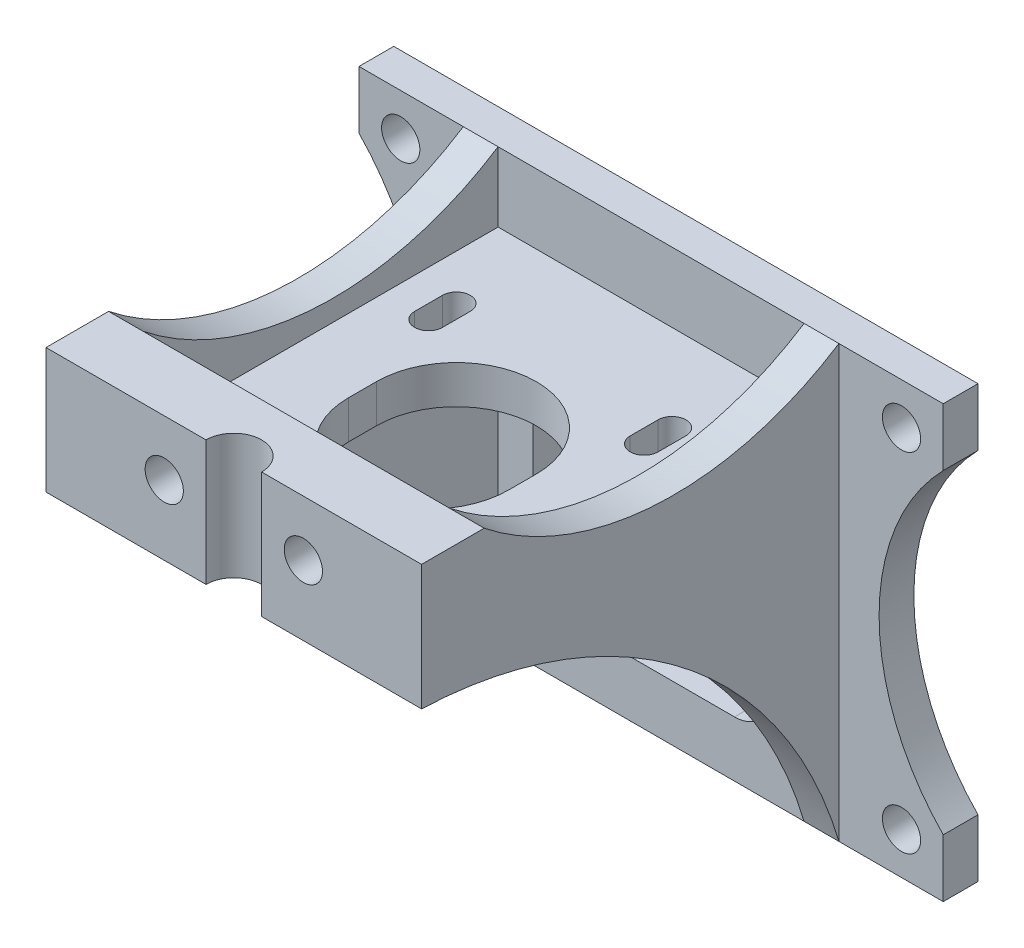
SolidWorks part; units mm, degrees
ref_plane "Front Plane" through (0, 0, 0) normal (0, 0, 1) x (1, 0, 0)
ref_plane "Top Plane" through (0, 0, 0) normal (0, 1, 0) x (1, 0, 0)
ref_plane "Right Plane" through (0, 0, 0) normal (1, 0, 0) x (0, 0, -1)
sketch "Sketch1" plane through (0, 0, 0) normal (1, 0, 0) x (0, 0, -1)
  line L0 (0, 0) -> (0, -62)
  line L1 (0, -62) -> (-5, -62)
  line L3 (-5, 0) -> (0, 0)
  line L4 (-56, 2.5) -> (-65, 2.5)
  line L5 (-65, 2.5) -> (-65, -15.5)
  arc A0 (-5, 0) -> (-56, 2.5) centre (-28.7567, 36.813) cw
  arc A1 (-5, -62) -> (-65, -15.5) centre (-67.324, -80.4584) ccw
  dimension "D3" = 51
  dimension "D5" = 43.813
  dimension "D8" = 65
  dimension "D1" = 5
  dimension "D2" = 62
  dimension "D4" = 2.5
  dimension "D6" = 9
  dimension "D7" = 18
  dimension "D9" = 5
extrude "Boss-Extrude1" add sketch "Sketch1" along normal blind 42 and the other way blind 42
sketch "Sketch2" plane through (0, 0, 0) normal (0, 0, -1) x (-1, 0, 0)
  line L0 (42, -62) -> (-42, -62) construction
  line L1 (-12, -54) -> (12, -54)
  line L2 (-17, -49) -> (-17, -25.5)
  line L3 (-12, -20.5) -> (12, -20.5)
  line L4 (17, -49) -> (17, -25.5)
  line L5 (42, -62) -> (42, 0) construction
  line L6 (42, 0) -> (-42, 0) construction
  line L7 (-42, -62) -> (-42, 0) construction
  line L8 (42, 2.5) -> (-42, 2.5) construction
  line L9 (-42, 0) -> (-27, 0)
  line L10 (-42, 0) -> (-42, 2.5)
  line L11 (-42, 2.5) -> (-27, 2.5)
  line L12 (-27, 0) -> (-27, 2.5)
  line L14 (42, 0) -> (27, 0)
  line L15 (42, 0) -> (42, 2.5)
  line L16 (42, 2.5) -> (27, 2.5)
  line L17 (27, 0) -> (27, 2.5)
  circle A0 centre (-36, -6) radius 2.75
  circle A1 centre (36, -6) radius 2.75
  circle A2 centre (36, -56) radius 2.75
  circle A3 centre (-36, -56) radius 2.75
  arc A4 (12, -20.5) -> (17, -25.5) centre (12, -25.5) cw
  arc A5 (12, -54) -> (17, -49) centre (12, -49) ccw
  arc A6 (-12, -54) -> (-17, -49) centre (-12, -49) cw
  arc A7 (-17, -25.5) -> (-12, -20.5) centre (-12, -25.5) cw
  arc A8 (-42, -8.3208) -> (-42, -53.6792) centre (-65.2788, -31) cw
  arc A9 (42, -8.3208) -> (42, -53.6792) centre (65.2788, -31) ccw
  line M7 (42, 0) -> (-42, 0)
  line M8 (-42, 0) -> (-42, -62)
  line M10 (42, -62) -> (42, 0)
  dimension "D1" = 5.5
  dimension "D2" = 5.5
  dimension "D3" = 5.5
  dimension "D4" = 5.5
  dimension "D9" = 5
  dimension "D18" = 8.3208
  dimension "D20" = 32.5
  dimension "D21" = 8.3208
  dimension "D23" = 32.5
  dimension "D5" = 33.5
  dimension "D6" = 34
  dimension "D7" = 8
  dimension "D8" = 25
  dimension "D10" = 6
  dimension "D11" = 6
  dimension "D12" = 6
  dimension "D13" = 6
  dimension "D14" = 6
  dimension "D15" = 6
  dimension "D16" = 6
  dimension "D17" = 6
  dimension "D19" = 8.3208
  dimension "D22" = 8.3208
  dimension "D24" = 15
  dimension "D25" = 15
extrude "Cut-Extrude1" cut sketch "Sketch2" against normal through all contours A0 | A8 M8 | A7 L2 A6 L1 A5 L4 A4 L3 | A3 | A2 | A1 | L17 L15 L16 M7 | L12 L11 L10 M7 | A9 M10 region at (0, -37.25, 0) region at (34.5, 1.25, 0) region at (-38.2626, -31, 0) region at (-34.5, 1.25, 0) region at (38.2626, -31, 0) region at (36, -6, 0) region at (-36, -6, 0) region at (-36, -56, 0) region at (36, -56, 0)
sketch "Sketch3" plane through (0, -62, 0) normal (0, -1, 0) x (-1, 0, 0)
  line L0 (42, -5) -> (27, -5)
  line L1 (42, -5) -> (-42, -5) construction
  line L2 (27, -5) -> (27, -65)
  line L3 (36.7131, -65) -> (-36.7131, -65) construction
  line L4 (0, -33) -> (0, -37) construction
  line L5 (-27, -65) -> (-27, -5)
  line L6 (-27, -5) -> (-42, -5)
  line L7 (-42, -5) -> (-42, -65)
  line L8 (-42, -65) -> (-27, -65)
  line L9 (42, -65) -> (42, -5)
  line L10 (42, -65) -> (27, -65)
  line L11 (11.5, -33) -> (11.5, -37)
  line L12 (-11.5, -33) -> (-11.5, -37)
  line L13 (15.5, -48.5) -> (15.5, -52.5) construction
  line L14 (17.5, -48.5) -> (17.5, -52.5)
  line L15 (13.5, -48.5) -> (13.5, -52.5)
  line L16 (15.5, -17.5) -> (15.5, -21.5) construction
  line L17 (17.5, -17.5) -> (17.5, -21.5)
  line L18 (13.5, -17.5) -> (13.5, -21.5)
  line L19 (42, 0) -> (-42, 0) construction
  line L20 (0, -65) -> (0, 0) construction
  line L21 (-15.5, -17.5) -> (-15.5, -21.5) construction
  line L22 (-17.5, -17.5) -> (-17.5, -21.5)
  line L23 (-13.5, -17.5) -> (-13.5, -21.5)
  line L24 (-15.5, -48.5) -> (-15.5, -52.5) construction
  line L25 (-17.5, -48.5) -> (-17.5, -52.5)
  line L26 (-13.5, -48.5) -> (-13.5, -52.5)
  circle A0 centre (0, -65) radius 4
  arc A1 (11.5, -33) -> (-11.5, -33) centre (0, -33) ccw
  arc A2 (-11.5, -37) -> (11.5, -37) centre (0, -37) ccw
  arc A3 (17.5, -48.5) -> (13.5, -48.5) centre (15.5, -48.5) ccw
  arc A4 (13.5, -52.5) -> (17.5, -52.5) centre (15.5, -52.5) ccw
  arc A5 (17.5, -17.5) -> (13.5, -17.5) centre (15.5, -17.5) ccw
  arc A6 (13.5, -21.5) -> (17.5, -21.5) centre (15.5, -21.5) ccw
  arc A7 (-17.5, -17.5) -> (-13.5, -17.5) centre (-15.5, -17.5) cw
  arc A8 (-13.5, -21.5) -> (-17.5, -21.5) centre (-15.5, -21.5) cw
  arc A9 (-17.5, -48.5) -> (-13.5, -48.5) centre (-15.5, -48.5) cw
  arc A10 (-13.5, -52.5) -> (-17.5, -52.5) centre (-15.5, -52.5) cw
  point P21 (0, -35)
  point P26 (15.5, -50.5)
  point P33 (15.5, -19.5)
  point P45 (-15.5, -19.5)
  point P52 (-15.5, -50.5)
  dimension "D3" = 8
  dimension "D4" = 11.5
  dimension "D9" = 2
  dimension "D10" = 2
  dimension "D1" = 15
  dimension "D2" = 15
  dimension "D5" = 4
  dimension "D6" = 28
  dimension "D7" = 4
  dimension "D8" = 4
  dimension "D11" = 12.5
  dimension "D12" = 11.5
  dimension "D13" = 17.5
extrude "Cut-Extrude2" cut sketch "Sketch3" against normal through all
sketch "Sketch4" plane through (0, 0, 65) normal (0, 0, 1) x (1, 0, 0)
  line L0 (-27, -62) -> (27, -62) construction
  line L1 (-22, -62) -> (22, -62)
  line L2 (-22, -62) -> (-22, -15.5)
  line L3 (-22, -15.5) -> (22, -15.5)
  line L4 (22, -62) -> (22, -15.5)
  line L5 (4, -15.5) -> (27, -15.5) construction
  line L6 (27, -62) -> (27, -15.5) construction
  line L7 (-27, -15.5) -> (-27, -62) construction
  dimension "D1" = 46.5
  dimension "D2" = 5
  dimension "D3" = 5
extrude "Cut-Extrude3" cut sketch "Sketch4" against normal blind 60
sketch "Sketch5" plane through (0, 0, 0) normal (0, 1, 0) x (1, 0, 0)
  line L0 (-27, -56) -> (27, -56) construction
  line L1 (-22, -56) -> (22, -56)
  line L2 (-22, -56) -> (-22, -5)
  line L3 (-22, -5) -> (22, -5)
  line L4 (22, -56) -> (22, -5)
  line L5 (-27, -5) -> (27, -5) construction
  line L6 (-27, -5) -> (-27, -56) construction
  line L7 (27, -56) -> (27, -5) construction
  dimension "D1" = 5
  dimension "D2" = 5
extrude "Cut-Extrude4" cut sketch "Sketch5" against normal blind 10 and the other way blind 10
sketch "Sketch6" plane through (0, 0, 65) normal (0, 0, 1) x (1, 0, 0)
  line L0 (-27, 2.5) -> (-4, 2.5) construction
  line L1 (4, 2.5) -> (27, 2.5) construction
  circle A0 centre (-10, -5.5) radius 2.75
  circle A1 centre (10, -5.5) radius 2.75
  dimension "D1" = 5.5
  dimension "D2" = 5.5
  dimension "D3" = 10
  dimension "D4" = 10
  dimension "D5" = 8
  dimension "D6" = 8
extrude "Cut-Extrude5" cut sketch "Sketch6" against normal blind 4.6
